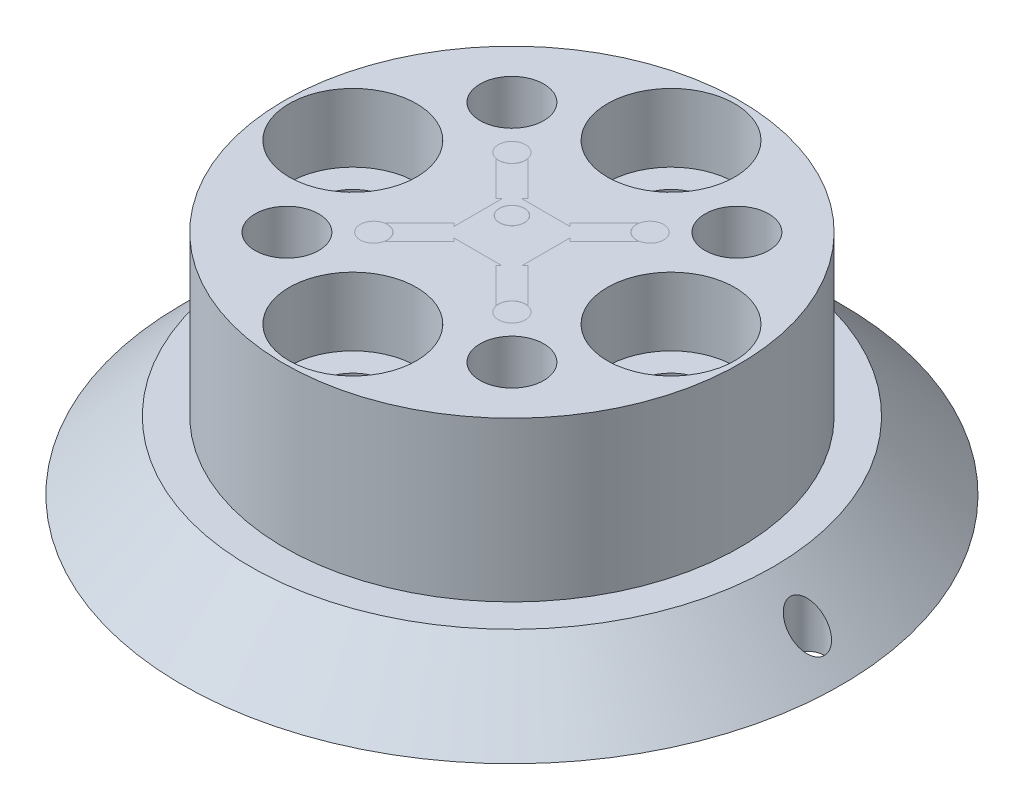
SolidWorks part; units mm, degrees
other "white_2"
other "white_4"
other "blue_1"
other "graphite_1"
other "white_3"
other "white"
other "white_5"
ref_plane "Front Plane" through (0, 0, 0) normal (0, 0, 1) x (1, 0, 0)
ref_plane "Top Plane" through (0, 0, 0) normal (0, 1, 0) x (1, 0, 0)
ref_plane "Right Plane" through (0, 0, 0) normal (1, 0, 0) x (0, 0, -1)
sketch "Sketch1" plane through (0, 0, 0) normal (0, 0, 1) x (1, 0, 0)
  line L0 (14.5, 0) -> (11.5, 3)
  line L1 (11.5, 3) -> (10.025, 3)
  line L2 (10.025, 3) -> (10.025, 10)
  line L3 (10.025, 10) -> (0, 10)
  line L4 (14.5, 0) -> (0, 0)
  line L5 (0, 10) -> (0, 0) construction
  line L6 (0, 10) -> (0, 0)
  dimension "D1" = 20.05
  dimension "D2" = 23
  dimension "D3" = 3
  dimension "D4" = 3
  dimension "D5" = 7
revolve "Revolve1" add sketch "Sketch1" angle 360 about L5
sketch "Sketch2" plane through (0, 10, 0) normal (0, 1, 0) x (1, 0, 0)
  line L0 (0, 0) -> (0, 7) construction
  circle A0 centre (0, 7) radius 1.4
  circle A1 centre (4.9497, 4.9497) radius 1.4
  circle A2 centre (7, 0) radius 1.4
  circle A3 centre (4.9497, -4.9497) radius 1.4
  circle A4 centre (0, -7) radius 1.4
  circle A5 centre (-4.9497, -4.9497) radius 1.4
  circle A6 centre (-7, 0) radius 1.4
  circle A7 centre (-4.9497, 4.9497) radius 1.4
  point P13 (0, 0)
  dimension "D1" = 2.8
  dimension "D2" = 7
  dimension "D3" = 8
extrude "Cut-Extrude1" cut sketch "Sketch2" against normal through all
hole_wizard "CBORE for M5 Hex Head Bolt1" positions "3DSketch1" profile "Sketch3" counterbore size "M5" standard "ANSI Metric" end condition through all
sketch3d "3DSketch1"
  line L0 (0, 0, -7) -> (0, 10, -7) construction
  line L1 (-7, 0, 0) -> (-7, 10, 0) construction
  line L2 (0, 0, 7) -> (0, 10, 7) construction
  line L3 (7, 0, 0) -> (7, 10, 0) construction
  point P0 (0, 10, -7)
  point P4 (-7, 10, 0)
  point P8 (0, 10, 7)
  point P12 (7, 10, 0)
sketch "Sketch3" plane through (0, 10, -7) normal (1, 0, 0) x (0, 0, 1)
  line L0 (0, 0) -> (0, 10)
  line L1 (0, 10) -> (1.6, 10)
  line L3 (1.6, 10) -> (1.6, 3)
  line L4 (1.6, 3) -> (2.8, 3)
  line L5 (2.8, 3) -> (2.8, 0)
  line L7 (2.8, 0) -> (0, 0)
  line L11 (0, -6.35) -> (0, 107.95) construction
  dimension "Thru Hole Dia." = 3.2
  dimension "Thru Hole Depth" = 10
  dimension "C'Bore Dia." = 5.6
  dimension "C'Bore Depth" = 3
sketch "Sketch4" plane through (0, 0, 0) normal (0, 1, 0) x (1, 0, 0)
  line L0 (0, 0) -> (13, 0) construction
  circle A0 centre (13, 0) radius 0.75
  dimension "D1" = 1.5
  dimension "D2" = 13
extrude "Cut-Extrude3" cut sketch "Sketch4" along normal through all
sketch "GL_end_blue" plane through (0, 0, 0) normal (0, 1, 0) x (1, 0, 0)
  line L0 (-0.9263, -1.6263) -> (-2.4462, -3.1463)
  line L1 (-2.4462, -3.1463) -> (-2.4355, -3.0404)
  line L2 (-2.4355, -3.0404) -> (-2.4616, -2.8649)
  line L3 (-2.4616, -2.8649) -> (-2.5374, -2.7045)
  line L4 (-2.5374, -2.7045) -> (-2.6128, -2.6126)
  line L5 (-2.6128, -2.6126) -> (-2.7552, -2.507)
  line L6 (-2.7552, -2.507) -> (-2.865, -2.4615)
  line L7 (-2.865, -2.4615) -> (-3.0404, -2.4355)
  line L8 (-3.0404, -2.4355) -> (-3.1463, -2.4462)
  line L9 (-3.1463, -2.4462) -> (-1.6263, -0.9263)
  line L10 (-1.6263, -0.9263) -> (-1.495, -1.0577)
  line L11 (-1.495, -1.0577) -> (-1.495, 1.0577)
  line L12 (-1.495, 1.0577) -> (-1.6263, 0.9263)
  line L13 (-1.6263, 0.9263) -> (-3.1463, 2.4462)
  line L14 (-3.1463, 2.4462) -> (-3.0404, 2.4355)
  line L15 (-3.0404, 2.4355) -> (-2.8649, 2.4616)
  line L16 (-2.8649, 2.4616) -> (-2.7045, 2.5374)
  line L17 (-2.7045, 2.5374) -> (-2.6126, 2.6128)
  line L18 (-2.6126, 2.6128) -> (-2.507, 2.7552)
  line L19 (-2.507, 2.7552) -> (-2.4615, 2.865)
  line L20 (-2.4615, 2.865) -> (-2.4355, 3.0404)
  line L21 (-2.4355, 3.0404) -> (-2.4462, 3.1463)
  line L22 (-2.4462, 3.1463) -> (-0.9263, 1.6263)
  line L23 (-0.9263, 1.6263) -> (-1.0577, 1.495)
  line L24 (-1.0577, 1.495) -> (1.0577, 1.495)
  line L25 (1.0577, 1.495) -> (0.9263, 1.6263)
  line L26 (0.9263, 1.6263) -> (2.4462, 3.1463)
  line L27 (2.4462, 3.1463) -> (2.4355, 3.0404)
  line L28 (2.4355, 3.0404) -> (2.4616, 2.8649)
  line L29 (2.4616, 2.8649) -> (2.5374, 2.7045)
  line L30 (2.5374, 2.7045) -> (2.6127, 2.6127)
  line L31 (2.6127, 2.6127) -> (2.7045, 2.5374)
  line L32 (2.7045, 2.5374) -> (2.8649, 2.4616)
  line L33 (2.8649, 2.4616) -> (3.0404, 2.4355)
  line L34 (3.0404, 2.4355) -> (3.1463, 2.4462)
  line L35 (3.1463, 2.4462) -> (1.6263, 0.9263)
  line L36 (1.6263, 0.9263) -> (1.495, 1.0577)
  line L37 (1.495, 1.0577) -> (1.495, -1.0577)
  line L38 (1.495, -1.0577) -> (1.6263, -0.9263)
  line L39 (1.6263, -0.9263) -> (3.1463, -2.4462)
  line L40 (3.1463, -2.4462) -> (3.0404, -2.4355)
  line L41 (3.0404, -2.4355) -> (2.865, -2.4615)
  line L42 (2.865, -2.4615) -> (2.7552, -2.507)
  line L43 (2.7552, -2.507) -> (2.6128, -2.6126)
  line L44 (2.6128, -2.6126) -> (2.5374, -2.7045)
  line L45 (2.5374, -2.7045) -> (2.4616, -2.8649)
  line L46 (2.4616, -2.8649) -> (2.4355, -3.0404)
  line L47 (2.4355, -3.0404) -> (2.4462, -3.1463)
  line L48 (2.4462, -3.1463) -> (0.9263, -1.6263)
  line L49 (0.9263, -1.6263) -> (1.0577, -1.495)
  line L50 (1.0577, -1.495) -> (-1.0577, -1.495)
  line L51 (-1.0577, -1.495) -> (-0.9263, -1.6263)
  line L52 (-0.084, 0.582) -> (-0.084, 0.6908)
  line L53 (-0.084, 0.6908) -> (-0.1053, 0.7975)
  line L54 (-0.1053, 0.7975) -> (-0.1469, 0.898)
  line L55 (-0.1469, 0.898) -> (-0.2074, 0.9885)
  line L56 (-0.2074, 0.9885) -> (-0.2843, 1.0654)
  line L57 (-0.2843, 1.0654) -> (-0.3748, 1.1259)
  line L58 (-0.3748, 1.1259) -> (-0.4753, 1.1675)
  line L59 (-0.4753, 1.1675) -> (-0.582, 1.1887)
  line L60 (-0.582, 1.1887) -> (-0.6908, 1.1887)
  line L61 (-0.6908, 1.1887) -> (-0.7975, 1.1675)
  line L62 (-0.7975, 1.1675) -> (-0.898, 1.1259)
  line L63 (-0.898, 1.1259) -> (-0.9885, 1.0654)
  line L64 (-0.9885, 1.0654) -> (-1.0654, 0.9885)
  line L65 (-1.0654, 0.9885) -> (-1.1259, 0.898)
  line L66 (-1.1259, 0.898) -> (-1.1675, 0.7975)
  line L67 (-1.1675, 0.7975) -> (-1.1887, 0.6908)
  line L68 (-1.1887, 0.6908) -> (-1.1887, 0.582)
  line L69 (-1.1887, 0.582) -> (-1.1675, 0.4753)
  line L70 (-1.1675, 0.4753) -> (-1.1259, 0.3748)
  line L71 (-1.1259, 0.3748) -> (-1.0654, 0.2843)
  line L72 (-1.0654, 0.2843) -> (-0.9885, 0.2074)
  line L73 (-0.9885, 0.2074) -> (-0.898, 0.1469)
  line L74 (-0.898, 0.1469) -> (-0.7975, 0.1053)
  line L75 (-0.7975, 0.1053) -> (-0.6908, 0.084)
  line L76 (-0.6908, 0.084) -> (-0.582, 0.084)
  line L77 (-0.582, 0.084) -> (-0.4753, 0.1053)
  line L78 (-0.4753, 0.1053) -> (-0.3748, 0.1469)
  line L79 (-0.3748, 0.1469) -> (-0.2843, 0.2074)
  line L80 (-0.2843, 0.2074) -> (-0.2074, 0.2843)
  line L81 (-0.2074, 0.2843) -> (-0.1469, 0.3748)
  line L82 (-0.1469, 0.3748) -> (-0.1053, 0.4753)
  line L83 (-0.1053, 0.4753) -> (-0.084, 0.582)
extrude "GL_end_blue_cut" cut sketch "GL_end_blue" along normal blind 1.1 from offset 9.4
extrude "GL_end_blue_inlay" add sketch "GL_end_blue<2>" along normal blind 0.6 from offset 9.4 separate body
sketch "GL_end_blue<2>" plane through (0, 0, 0) normal (0, 1, 0) x (1, 0, 0) same geometry as "GL_end_blue"
sketch "GL_end_white" plane through (0, 0, 0) normal (0, 1, 0) x (1, 0, 0)
  line L0 (3.5353, -3.3711) -> (3.4613, -3.4613)
  line L1 (3.4613, -3.4613) -> (3.3711, -3.5353)
  line L2 (3.3711, -3.5353) -> (3.2682, -3.5902)
  line L3 (3.2682, -3.5902) -> (3.1566, -3.6241)
  line L4 (3.1566, -3.6241) -> (3.0406, -3.6355)
  line L5 (3.0406, -3.6355) -> (2.9245, -3.6241)
  line L6 (2.9245, -3.6241) -> (2.8129, -3.5902)
  line L7 (2.8129, -3.5902) -> (2.71, -3.5353)
  line L8 (2.71, -3.5353) -> (2.6198, -3.4613)
  line L9 (2.6198, -3.4613) -> (2.5459, -3.3711)
  line L10 (2.5459, -3.3711) -> (2.4909, -3.2682)
  line L11 (2.4909, -3.2682) -> (2.457, -3.1566)
  line L12 (2.457, -3.1566) -> (2.4456, -3.0406)
  line L13 (2.4456, -3.0406) -> (2.457, -2.9245)
  line L14 (2.457, -2.9245) -> (2.4909, -2.8129)
  line L15 (2.4909, -2.8129) -> (2.5459, -2.71)
  line L16 (2.5459, -2.71) -> (2.6198, -2.6198)
  line L17 (2.6198, -2.6198) -> (2.71, -2.5459)
  line L18 (2.71, -2.5459) -> (2.8129, -2.4909)
  line L19 (2.8129, -2.4909) -> (2.9245, -2.457)
  line L20 (2.9245, -2.457) -> (3.0406, -2.4456)
  line L21 (3.0406, -2.4456) -> (3.1566, -2.457)
  line L22 (3.1566, -2.457) -> (3.2682, -2.4909)
  line L23 (3.2682, -2.4909) -> (3.3711, -2.5459)
  line L24 (3.3711, -2.5459) -> (3.4613, -2.6198)
  line L25 (3.4613, -2.6198) -> (3.5353, -2.71)
  line L26 (3.5353, -2.71) -> (3.5902, -2.8129)
  line L27 (3.5902, -2.8129) -> (3.6241, -2.9245)
  line L28 (3.6241, -2.9245) -> (3.6355, -3.0406)
  line L29 (3.6355, -3.0406) -> (3.6241, -3.1566)
  line L30 (3.6241, -3.1566) -> (3.5902, -3.2682)
  line L31 (3.5902, -3.2682) -> (3.5353, -3.3711)
  line L32 (-2.5459, -3.3711) -> (-2.6198, -3.4613)
  line L33 (-2.6198, -3.4613) -> (-2.71, -3.5353)
  line L34 (-2.71, -3.5353) -> (-2.8129, -3.5902)
  line L35 (-2.8129, -3.5902) -> (-2.9245, -3.6241)
  line L36 (-2.9245, -3.6241) -> (-3.0406, -3.6355)
  line L37 (-3.0406, -3.6355) -> (-3.1566, -3.6241)
  line L38 (-3.1566, -3.6241) -> (-3.2682, -3.5902)
  line L39 (-3.2682, -3.5902) -> (-3.3711, -3.5353)
  line L40 (-3.3711, -3.5353) -> (-3.4613, -3.4613)
  line L41 (-3.4613, -3.4613) -> (-3.5353, -3.3711)
  line L42 (-3.5353, -3.3711) -> (-3.5902, -3.2682)
  line L43 (-3.5902, -3.2682) -> (-3.6241, -3.1566)
  line L44 (-3.6241, -3.1566) -> (-3.6355, -3.0406)
  line L45 (-3.6355, -3.0406) -> (-3.6241, -2.9245)
  line L46 (-3.6241, -2.9245) -> (-3.5902, -2.8129)
  line L47 (-3.5902, -2.8129) -> (-3.5353, -2.71)
  line L48 (-3.5353, -2.71) -> (-3.4613, -2.6198)
  line L49 (-3.4613, -2.6198) -> (-3.3711, -2.5459)
  line L50 (-3.3711, -2.5459) -> (-3.2682, -2.4909)
  line L51 (-3.2682, -2.4909) -> (-3.1566, -2.457)
  line L52 (-3.1566, -2.457) -> (-3.0406, -2.4456)
  line L53 (-3.0406, -2.4456) -> (-2.9245, -2.457)
  line L54 (-2.9245, -2.457) -> (-2.8129, -2.4909)
  line L55 (-2.8129, -2.4909) -> (-2.71, -2.5459)
  line L56 (-2.71, -2.5459) -> (-2.6198, -2.6198)
  line L57 (-2.6198, -2.6198) -> (-2.5459, -2.71)
  line L58 (-2.5459, -2.71) -> (-2.4909, -2.8129)
  line L59 (-2.4909, -2.8129) -> (-2.457, -2.9245)
  line L60 (-2.457, -2.9245) -> (-2.4456, -3.0406)
  line L61 (-2.4456, -3.0406) -> (-2.457, -3.1566)
  line L62 (-2.457, -3.1566) -> (-2.4909, -3.2682)
  line L63 (-2.4909, -3.2682) -> (-2.5459, -3.3711)
  line L64 (-0.1833, 0.3336) -> (-0.251, 0.251)
  line L65 (-0.251, 0.251) -> (-0.3336, 0.1833)
  line L66 (-0.3336, 0.1833) -> (-0.4278, 0.1329)
  line L67 (-0.4278, 0.1329) -> (-0.5301, 0.1019)
  line L68 (-0.5301, 0.1019) -> (-0.6364, 0.0914)
  line L69 (-0.6364, 0.0914) -> (-0.7427, 0.1019)
  line L70 (-0.7427, 0.1019) -> (-0.8449, 0.1329)
  line L71 (-0.8449, 0.1329) -> (-0.9392, 0.1833)
  line L72 (-0.9392, 0.1833) -> (-1.0218, 0.251)
  line L73 (-1.0218, 0.251) -> (-1.0895, 0.3336)
  line L74 (-1.0895, 0.3336) -> (-1.1399, 0.4278)
  line L75 (-1.1399, 0.4278) -> (-1.1709, 0.5301)
  line L76 (-1.1709, 0.5301) -> (-1.1814, 0.6364)
  line L77 (-1.1814, 0.6364) -> (-1.1709, 0.7427)
  line L78 (-1.1709, 0.7427) -> (-1.1399, 0.8449)
  line L79 (-1.1399, 0.8449) -> (-1.0895, 0.9392)
  line L80 (-1.0895, 0.9392) -> (-1.0218, 1.0218)
  line L81 (-1.0218, 1.0218) -> (-0.9392, 1.0895)
  line L82 (-0.9392, 1.0895) -> (-0.8449, 1.1399)
  line L83 (-0.8449, 1.1399) -> (-0.7427, 1.1709)
  line L84 (-0.7427, 1.1709) -> (-0.6364, 1.1814)
  line L85 (-0.6364, 1.1814) -> (-0.5301, 1.1709)
  line L86 (-0.5301, 1.1709) -> (-0.4278, 1.1399)
  line L87 (-0.4278, 1.1399) -> (-0.3336, 1.0895)
  line L88 (-0.3336, 1.0895) -> (-0.251, 1.0218)
  line L89 (-0.251, 1.0218) -> (-0.1833, 0.9392)
  line L90 (-0.1833, 0.9392) -> (-0.1329, 0.8449)
  line L91 (-0.1329, 0.8449) -> (-0.1019, 0.7427)
  line L92 (-0.1019, 0.7427) -> (-0.0914, 0.6364)
  line L93 (-0.0914, 0.6364) -> (-0.1019, 0.5301)
  line L94 (-0.1019, 0.5301) -> (-0.1329, 0.4278)
  line L95 (-0.1329, 0.4278) -> (-0.1833, 0.3336)
  line L96 (-2.6198, 2.6198) -> (-2.71, 2.5459)
  line L97 (-2.71, 2.5459) -> (-2.8129, 2.4909)
  line L98 (-2.8129, 2.4909) -> (-2.9245, 2.457)
  line L99 (-2.9245, 2.457) -> (-3.0406, 2.4456)
  line L100 (-3.0406, 2.4456) -> (-3.1566, 2.457)
  line L101 (-3.1566, 2.457) -> (-3.2682, 2.4909)
  line L102 (-3.2682, 2.4909) -> (-3.3711, 2.5459)
  line L103 (-3.3711, 2.5459) -> (-3.4613, 2.6198)
  line L104 (-3.4613, 2.6198) -> (-3.5353, 2.71)
  line L105 (-3.5353, 2.71) -> (-3.5902, 2.8129)
  line L106 (-3.5902, 2.8129) -> (-3.6241, 2.9245)
  line L107 (-3.6241, 2.9245) -> (-3.6355, 3.0406)
  line L108 (-3.6355, 3.0406) -> (-3.6241, 3.1566)
  line L109 (-3.6241, 3.1566) -> (-3.5902, 3.2682)
  line L110 (-3.5902, 3.2682) -> (-3.5353, 3.3711)
  line L111 (-3.5353, 3.3711) -> (-3.4613, 3.4613)
  line L112 (-3.4613, 3.4613) -> (-3.3711, 3.5353)
  line L113 (-3.3711, 3.5353) -> (-3.2682, 3.5902)
  line L114 (-3.2682, 3.5902) -> (-3.1566, 3.6241)
  line L115 (-3.1566, 3.6241) -> (-3.0406, 3.6355)
  line L116 (-3.0406, 3.6355) -> (-2.9245, 3.6241)
  line L117 (-2.9245, 3.6241) -> (-2.8129, 3.5902)
  line L118 (-2.8129, 3.5902) -> (-2.71, 3.5353)
  line L119 (-2.71, 3.5353) -> (-2.6198, 3.4613)
  line L120 (-2.6198, 3.4613) -> (-2.5459, 3.3711)
  line L121 (-2.5459, 3.3711) -> (-2.4909, 3.2682)
  line L122 (-2.4909, 3.2682) -> (-2.457, 3.1566)
  line L123 (-2.457, 3.1566) -> (-2.4456, 3.0406)
  line L124 (-2.4456, 3.0406) -> (-2.457, 2.9245)
  line L125 (-2.457, 2.9245) -> (-2.4909, 2.8129)
  line L126 (-2.4909, 2.8129) -> (-2.5459, 2.71)
  line L127 (-2.5459, 2.71) -> (-2.6198, 2.6198)
  line L128 (3.4613, 2.6198) -> (3.3711, 2.5459)
  line L129 (3.3711, 2.5459) -> (3.2682, 2.4909)
  line L130 (3.2682, 2.4909) -> (3.1566, 2.457)
  line L131 (3.1566, 2.457) -> (3.0406, 2.4456)
  line L132 (3.0406, 2.4456) -> (2.9245, 2.457)
  line L133 (2.9245, 2.457) -> (2.8129, 2.4909)
  line L134 (2.8129, 2.4909) -> (2.71, 2.5459)
  line L135 (2.71, 2.5459) -> (2.6198, 2.6198)
  line L136 (2.6198, 2.6198) -> (2.5459, 2.71)
  line L137 (2.5459, 2.71) -> (2.4909, 2.8129)
  line L138 (2.4909, 2.8129) -> (2.457, 2.9245)
  line L139 (2.457, 2.9245) -> (2.4456, 3.0406)
  line L140 (2.4456, 3.0406) -> (2.457, 3.1566)
  line L141 (2.457, 3.1566) -> (2.4909, 3.2682)
  line L142 (2.4909, 3.2682) -> (2.5459, 3.3711)
  line L143 (2.5459, 3.3711) -> (2.6198, 3.4613)
  line L144 (2.6198, 3.4613) -> (2.71, 3.5353)
  line L145 (2.71, 3.5353) -> (2.8129, 3.5902)
  line L146 (2.8129, 3.5902) -> (2.9245, 3.6241)
  line L147 (2.9245, 3.6241) -> (3.0406, 3.6355)
  line L148 (3.0406, 3.6355) -> (3.1566, 3.6241)
  line L149 (3.1566, 3.6241) -> (3.2682, 3.5902)
  line L150 (3.2682, 3.5902) -> (3.3711, 3.5353)
  line L151 (3.3711, 3.5353) -> (3.4613, 3.4613)
  line L152 (3.4613, 3.4613) -> (3.5353, 3.3711)
  line L153 (3.5353, 3.3711) -> (3.5902, 3.2682)
  line L154 (3.5902, 3.2682) -> (3.6241, 3.1566)
  line L155 (3.6241, 3.1566) -> (3.6355, 3.0406)
  line L156 (3.6355, 3.0406) -> (3.6241, 2.9245)
  line L157 (3.6241, 2.9245) -> (3.5902, 2.8129)
  line L158 (3.5902, 2.8129) -> (3.5353, 2.71)
  line L159 (3.5353, 2.71) -> (3.4613, 2.6198)
extrude "GL_end_white_cut" cut sketch "GL_end_white" along normal blind 1.1 from offset 9.4
extrude "GL_end_white_inlay" add sketch "GL_end_white<2>" along normal blind 0.6 from offset 9.4 separate body
sketch "GL_end_white<2>" plane through (0, 0, 0) normal (0, 1, 0) x (1, 0, 0) same geometry as "GL_end_white"
